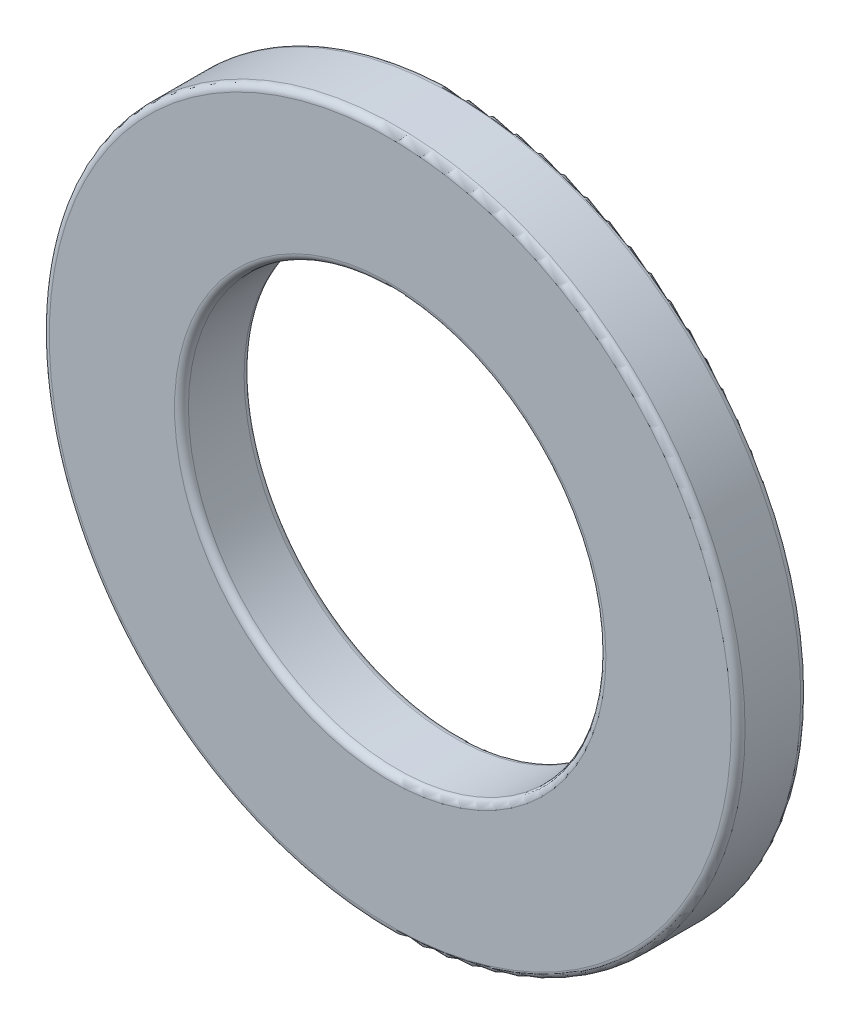
SolidWorks part; units mm, degrees
ref_plane "Front Plane" through (0, 0, 0) normal (0, 0, 1) x (1, 0, 0)
ref_plane "Top Plane" through (0, 0, 0) normal (0, 1, 0) x (1, 0, 0)
ref_plane "Right Plane" through (0, 0, 0) normal (1, 0, 0) x (0, 0, -1)
sketch "Sketch1" plane through (0, 0, 0) normal (0, 0, 1) x (1, 0, 0)
  line L0 (-15.875, 0) -> (-9.525, 0) construction
  line L1 (-9.525, 0) -> (9.525, 0) construction
  line L2 (9.525, 0) -> (15.875, 0) construction
  line L3 (0, 15.875) -> (0, -15.875) construction
  circle A0 centre (0, 0) radius 9.525 construction
  circle A1 centre (0, 0) radius 15.875 construction
  point P11 (9.525, 0)
  point P12 (-9.525, 0)
  dimension "ID" = 19.05
  dimension "OD" = 31.75
sketch "Sketch2" plane through (0, 0, 0) normal (1, 0, 0) x (0, 0, -1)
  line L1 (-1.5875, -15.875) -> (1.5875, -15.875) construction
  line L2 (-1.5875, -15.875) -> (-1.5875, 15.875) construction
  line L3 (-1.5875, 15.875) -> (1.5875, 15.875) construction
  line L4 (1.5875, -15.875) -> (1.5875, 15.875) construction
  line L5 (-1.5875, -15.875) -> (1.5875, 15.875) construction
  line L6 (-1.5875, 15.875) -> (1.5875, -15.875) construction
  point P0 (0, 0)
  dimension "Thickness" = 3.175
sketch "Sketch3" plane through (0, 0, 0) normal (0, 0, 1) x (1, 0, 0)
  circle A0 centre (0, 0) radius 9.525 construction
  circle A1 centre (0, 0) radius 15.875 construction
  circle A2 centre (0, 0) radius 9.525
  circle A3 centre (0, 0) radius 15.875
extrude "Boss-Extrude1" add sketch "Sketch3" along normal up to vertex (1.5875 mm away) and the other way up to vertex (1.5875 mm away) up to point (0, 15.875, 1.5875) other way up to point (0, 15.875, -1.5875)
fillet "Fillet1" radius 0.3175 4 edges at (15.875, 0, -1.5875) (9.525, 0, -1.5875) (9.525, 0, 1.5875) (15.875, 0, 1.5875)
equation "\"D1@Fillet1\"=\"Thickness@Sketch2\"*.1"
